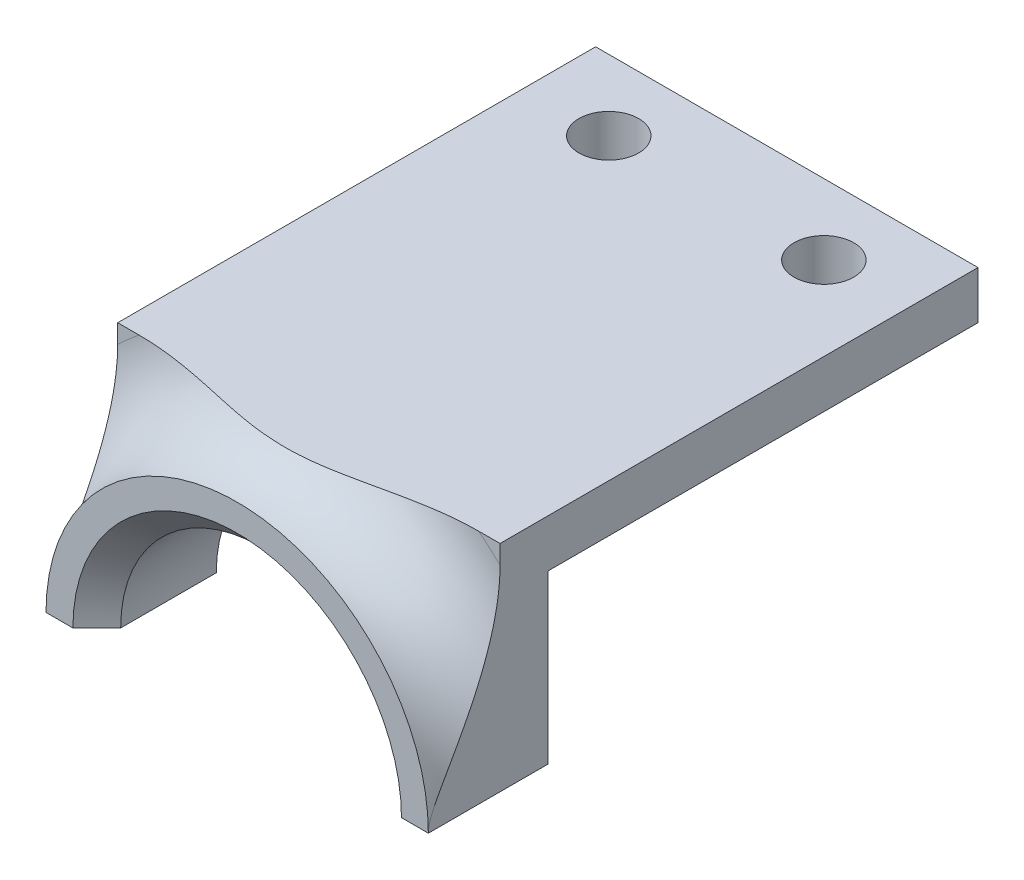
SolidWorks part; units mm, degrees
ref_plane "Plan de face" through (0, 0, 0) normal (0, 0, 1) x (1, 0, 0)
ref_plane "Plan de dessus" through (0, 0, 0) normal (0, 1, 0) x (1, 0, 0)
ref_plane "Plan de droite" through (0, 0, 0) normal (1, 0, 0) x (0, 0, -1)
sketch "Esquisse1" plane through (0, 0, 0) normal (0, 0, 1) x (1, 0, 0)
  line L0 (0, 0) -> (0, 18) construction
  line L1 (-16, 18) -> (16, 18)
  line L2 (-16, 18) -> (-16, 0)
  line L3 (-16, 0) -> (-11.75, 0)
  line L4 (16, 18) -> (16, 0)
  line L5 (11.75, 0) -> (16, 0)
  line L6 (-16, 0) -> (16, 0) construction
  arc A0 (11.75, 0) -> (-11.75, 0) centre (0, 0) ccw
  dimension "D1" = 23.5
  dimension "D2" = 32
  dimension "D3" = 18
extrude "Boss.-Extru.1" add sketch "Esquisse1" along normal blind 4
sketch "Esquisse2" plane through (0, 0, 0) normal (0, 0, -1) x (-1, 0, 0)
  line L0 (16, 18) -> (16, 0) construction
  line L1 (-16, 18) -> (16, 18)
  line L2 (-16, 18) -> (-16, 14)
  line L3 (-16, 14) -> (16, 14)
  line L4 (16, 18) -> (16, 14)
  dimension "D1" = 4
extrude "Boss.-Extru.2" add sketch "Esquisse2" along normal blind 36
sketch "Esquisse3" plane through (0, 0, 4) normal (0, 0, 1) x (1, 0, 0)
  line L0 (11.75, 0) -> (16, 0) construction
  line L1 (16, 0) -> (16, 18) construction
  line L2 (-16, 0) -> (-11.75, 0)
  line L3 (11.75, 0) -> (16, 0)
  arc A0 (-11.75, 0) -> (11.75, 0) centre (0, 0) cw
  arc A1 (-16, 0) -> (16, 0) centre (0, 0) cw
extrude "Boss.-Extru.3" add sketch "Esquisse3" along normal blind 6
fillet "Congé1" radius 7 1 edges at (0, 16, 4)
chamfer "Chanfrein1" distance 2 angle 45 1 edges at (0, 11.75, 10)
sketch "Esquisse4" plane through (0, 18, 0) normal (0, 1, 0) x (1, 0, 0)
  circle A0 centre (9, 30.1) radius 2.5
  circle A1 centre (-9, 30.1) radius 2.5
  dimension "D1" = 5
  dimension "D2" = 5
extrude "Enlèv. mat.-Extru.1" cut sketch "Esquisse4" against normal blind 10
